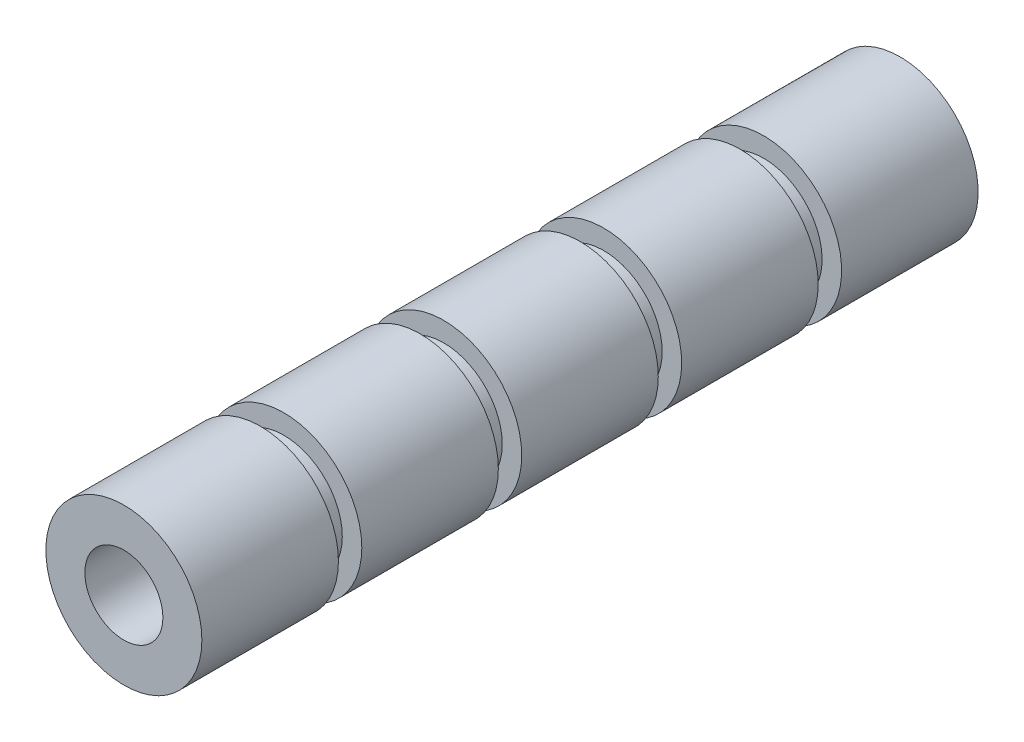
SolidWorks part; units mm, degrees
ref_plane "Front Plane" through (0, 0, 0) normal (0, 0, 1) x (1, 0, 0)
ref_plane "Top Plane" through (0, 0, 0) normal (0, 1, 0) x (1, 0, 0)
ref_plane "Right Plane" through (0, 0, 0) normal (1, 0, 0) x (0, 0, -1)
sketch "Sketch1" plane through (0, 0, 0) normal (0, 0, 1) x (1, 0, 0)
  circle A0 centre (0, 0) radius 7.5
  circle A1 centre (0, 0) radius 5
  dimension "D1" = 15
  dimension "D2" = 10
extrude "Boss-Extrude1" add sketch "Sketch1" along normal blind 99
sketch "Sketch2" plane through (0, 0, 0) normal (0, 0, -1) x (-1, 0, 0)
  circle A0 centre (0, 0) radius 10
  dimension "D1" = 20
extrude "Boss-Extrude2" add sketch "Sketch2" against normal blind 17.5
ref_plane "Plane1" through (0, 0, 20.5) normal (0, 0, 1) x (1, 0, 0)
sketch "Sketch3" plane through (0, 0, 20.5) normal (0, 0, 1) x (1, 0, 0)
  circle A0 centre (0, 0) radius 10 construction
  circle A1 centre (0, 0) radius 7.5 construction
  circle A2 centre (0, 0) radius 10
  circle A3 centre (0, 0) radius 7.5
extrude "Boss-Extrude3" add sketch "Sketch3" along normal blind 17.5
ref_plane "Plane2" through (0, 0, 41) normal (0, 0, 1) x (1, 0, 0)
sketch "Sketch4" plane through (0, 0, 41) normal (0, 0, 1) x (1, 0, 0)
  circle A0 centre (0, 0) radius 7.5 construction
  circle A1 centre (0, 0) radius 10 construction
  circle A2 centre (0, 0) radius 7.5
  circle A3 centre (0, 0) radius 10
extrude "Boss-Extrude4" add sketch "Sketch4" along normal blind 17.5
ref_plane "Plane3" through (0, 0, 61.5) normal (0, 0, 1) x (1, 0, 0)
sketch "Sketch5" plane through (0, 0, 61.5) normal (0, 0, 1) x (1, 0, 0)
  circle A0 centre (0, 0) radius 10 construction
  circle A1 centre (0, 0) radius 7.5 construction
  circle A2 centre (0, 0) radius 10
  circle A3 centre (0, 0) radius 7.5
extrude "Boss-Extrude5" add sketch "Sketch5" along normal blind 17.5
ref_plane "Plane4" through (0, 0, 82) normal (0, 0, 1) x (1, 0, 0)
sketch "Sketch6" plane through (0, 0, 82) normal (0, 0, 1) x (1, 0, 0)
  circle A0 centre (0, 0) radius 10 construction
  circle A1 centre (0, 0) radius 7.5 construction
  circle A2 centre (0, 0) radius 10
  circle A3 centre (0, 0) radius 7.5
extrude "Boss-Extrude6" add sketch "Sketch6" along normal blind 17.5
sketch "Sketch9" plane through (0, 0, 99) normal (0, 0, 1) x (1, 0, 0)
  circle A1 centre (0, 0) radius 7.5
  circle A2 centre (0, 0) radius 7.5
  circle A3 centre (0, 0) radius 5 construction
  circle A4 centre (0, 0) radius 5
  dimension "D1" = 0
extrude "Boss-Extrude7" add sketch "Sketch9" along normal up to surface (0.5 mm away) up to face at (10, 0, 99.5)
sketch "Sketch10" plane through (0, 0, 17.5) normal (0, 0, 1) x (1, 0, 0)
  circle A1 centre (0, 0) radius 5
  circle A2 centre (0, 0) radius 5
  dimension "D1" = 0
extrude "Cut-Extrude1" cut sketch "Sketch10" against normal through all
